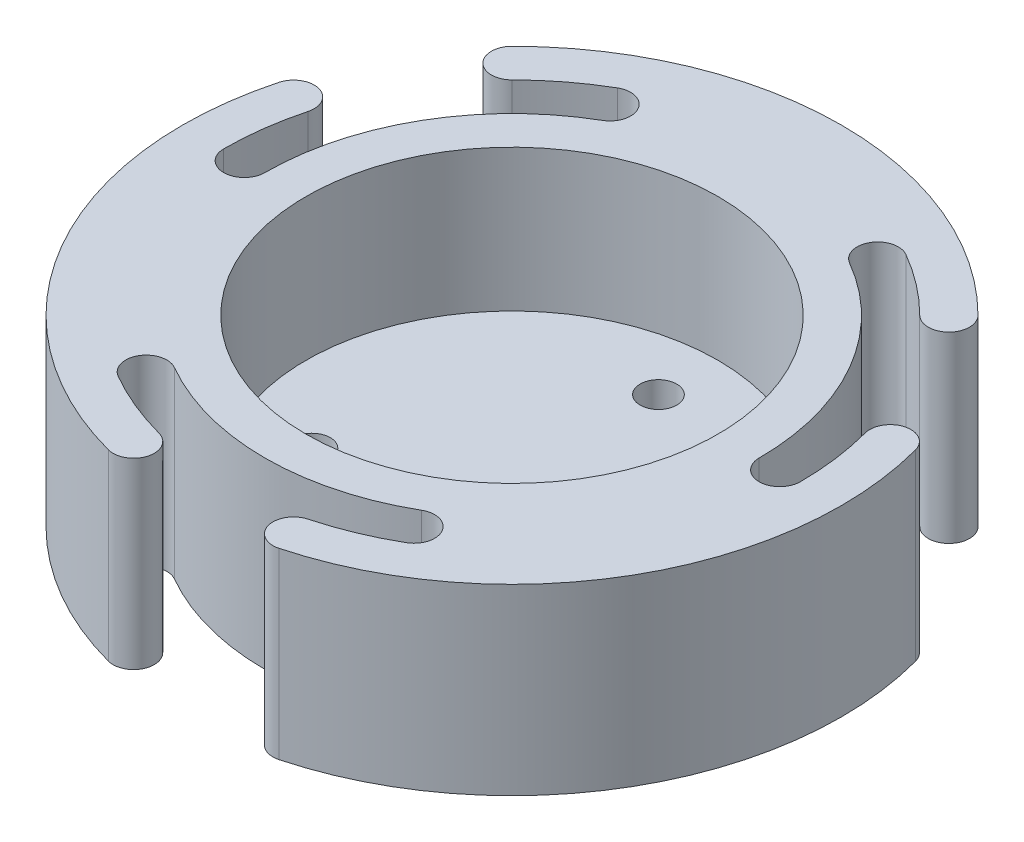
SolidWorks part; units mm, degrees
material "Alliage 1060"
ref_plane "Plan de face" through (0, 0, 0) normal (0, 0, 1) x (1, 0, 0)
ref_plane "Plan de dessus" through (0, 0, 0) normal (0, 1, 0) x (1, 0, 0)
ref_plane "Plan de droite" through (0, 0, 0) normal (1, 0, 0) x (0, 0, -1)
sketch "Esquisse1" plane through (0, 0, 0) normal (0, 1, 0) x (1, 0, 0)
  circle A0 centre (0, 0) radius 22.5
  circle A1 centre (0, 0) radius 40 construction
  circle A2 centre (0, 0) radius 36 construction
  circle A3 centre (0, 0) radius 31.5
  circle A4 centre (0, 0) radius 27 construction
  dimension "D1" = 45
  dimension "D2" = 80
  dimension "D3" = 72
  dimension "D4" = 63
  dimension "D5" = 54
extrude "Boss.-Extru.1" add sketch "Esquisse1" along normal blind 20
sketch "Esquisse2" plane through (0, 20, 0) normal (0, 1, 0) x (1, 0, 0)
  line L0 (-14.625, 25.3312) -> (0, 0) construction
  line L1 (0, 0) -> (-29.25, 0) construction
  line L2 (0, 0) -> (0, 31.5) construction
  arc A0 (-29.25, 0) -> (-14.625, 25.3312) centre (0, 0) cw construction
  arc A1 (-15.75, 27.2798) -> (-31.5, 0) centre (0, 0) ccw
  arc A2 (-13.5, 23.3827) -> (-27, 0) centre (0, 0) ccw
  arc A3 (-13.5, 23.3827) -> (-15.75, 27.2798) centre (-14.625, 25.3312) ccw
  arc A4 (-31.5, 0) -> (-27, 0) centre (-29.25, 0) ccw
  circle A5 centre (0, 0) radius 31.5 construction
  arc A6 (14.625, 25.3312) -> (29.25, 0) centre (0, 0) cw construction
  arc A7 (31.5, 0) -> (15.75, 27.2798) centre (0, 0) ccw
  arc A8 (27, 0) -> (13.5, 23.3827) centre (0, 0) ccw
  arc A9 (27, 0) -> (31.5, 0) centre (29.25, 0) ccw
  arc A10 (15.75, 27.2798) -> (13.5, 23.3827) centre (14.625, 25.3312) ccw
  arc A11 (14.625, -25.3312) -> (-14.625, -25.3312) centre (0, 0) cw construction
  arc A12 (-15.75, -27.2798) -> (15.75, -27.2798) centre (0, 0) ccw
  arc A13 (-13.5, -23.3827) -> (13.5, -23.3827) centre (0, 0) ccw
  arc A14 (-13.5, -23.3827) -> (-15.75, -27.2798) centre (-14.625, -25.3312) ccw
  arc A15 (15.75, -27.2798) -> (13.5, -23.3827) centre (14.625, -25.3312) ccw
  point P4 (-25.3312, 14.625)
  point P21 (25.3312, 14.625)
  point P28 (0, -29.25)
  point P33 (0, 0)
  dimension "D1" = 2.25
  dimension "D2" = 60
  dimension "D3" = 30
extrude "Enlèv. mat.-Extru.1" cut sketch "Esquisse2" against normal through all
sketch "Esquisse3" plane through (0, 20, 0) normal (0, 1, 0) x (1, 0, 0)
  line L0 (0, 33.75) -> (0, 0) construction
  line L1 (-23.8649, 23.8649) -> (0, 0) construction
  arc A0 (-23.8649, 23.8649) -> (23.8649, 23.8649) centre (0, 0) cw construction
  arc A1 (25.4558, 25.4558) -> (-25.4558, 25.4558) centre (0, 0) ccw
  arc A2 (22.2739, 22.2739) -> (-22.2739, 22.2739) centre (0, 0) ccw
  arc A3 (22.2739, 22.2739) -> (25.4558, 25.4558) centre (23.8649, 23.8649) ccw
  arc A4 (-25.4558, 25.4558) -> (-22.2739, 22.2739) centre (-23.8649, 23.8649) ccw
  arc A5 (15.75, 27.2798) -> (-15.75, 27.2798) centre (0, 0) ccw construction
  arc A6 (32.6, 8.7351) -> (8.7351, -32.6) centre (0, 0) cw construction
  arc A7 (9.3175, -34.7733) -> (34.7733, 9.3175) centre (0, 0) ccw
  arc A8 (8.1528, -30.4267) -> (30.4267, 8.1528) centre (0, 0) ccw
  arc A9 (8.1528, -30.4267) -> (9.3175, -34.7733) centre (8.7351, -32.6) ccw
  arc A10 (34.7733, 9.3175) -> (30.4267, 8.1528) centre (32.6, 8.7351) ccw
  arc A11 (-8.7351, -32.6) -> (-32.6, 8.7351) centre (0, 0) cw construction
  arc A12 (-34.7733, 9.3175) -> (-9.3175, -34.7733) centre (0, 0) ccw
  arc A13 (-30.4267, 8.1528) -> (-8.1528, -30.4267) centre (0, 0) ccw
  arc A14 (-30.4267, 8.1528) -> (-34.7733, 9.3175) centre (-32.6, 8.7351) ccw
  arc A15 (-9.3175, -34.7733) -> (-8.1528, -30.4267) centre (-8.7351, -32.6) ccw
  point P4 (0, 33.75)
  point P19 (29.2284, -16.875)
  point P26 (-29.2284, -16.875)
  point P31 (0, 0)
  dimension "D1" = 2.25
  dimension "D2" = 45
extrude "Boss.-Extru.2" add sketch "Esquisse3" against normal up to surface (20 mm away) up to face at (0, 0, 0)
sketch "Esquisse4" plane through (0, 0, 0) normal (0, -1, 0) x (1, 0, 0)
  circle A0 centre (0, 0) radius 22.5
extrude "Boss.-Extru.3" add sketch "Esquisse4" against normal blind 4.5
sketch "Esquisse5" plane through (0, 4.5, 0) normal (0, 1, 0) x (1, 0, 0)
  line L0 (0, 0) -> (0, 16) construction
  circle A0 centre (0, 16) radius 2
  circle A1 centre (13.8564, -8) radius 2
  circle A2 centre (-13.8564, -8) radius 2
  point P5 (0, 0)
  point P6 (45.4425, -9.4133)
  point P7 (0, 0)
  point P12 (0, 0)
  point P13 (0, 0)
  dimension "D2" = 4
  dimension "D1" = 16
  dimension "D3" = 3
extrude "Enlèv. mat.-Extru.2" cut sketch "Esquisse5" against normal up to next
